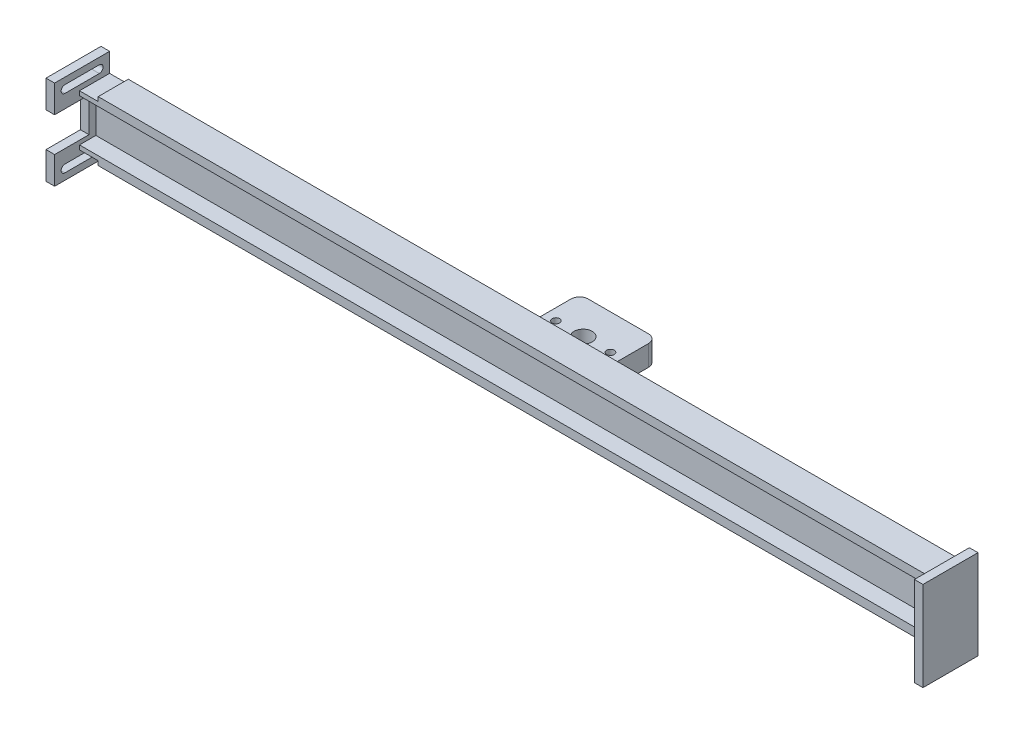
SolidWorks part; units mm, degrees
material "PLA"
ref_plane "Front Plane" through (0, 0, 0) normal (1, 0, 0) x (0, 1, 0)
ref_plane "Top Plane" through (0, 0, 0) normal (0, 0, 1) x (0, 1, 0)
ref_plane "Right Plane" through (0, 0, 0) normal (0, 1, 0) x (-1, 0, 0)
sketch "Sketch1" plane through (0, 0, 0) normal (1, 0, 0) x (0, 1, 0)
  line L16 (0, 4.7625) -> (-2.5, 4.7625)
  line L17 (0, 0) -> (12.3825, 0)
  line L18 (0, 0) -> (0, 4.7625)
  line L19 (0, 4.7625) -> (12.3825, 4.7625) construction
  line L20 (12.3825, 0) -> (12.3825, 4.7625)
  line L21 (-2.5, 4.7625) -> (-2.5, -4)
  line L22 (-2.5, -4) -> (14.8825, -4)
  line L23 (14.8825, -4) -> (14.8825, 4.7625)
  line L24 (12.3825, 4.7625) -> (14.8825, 4.7625)
  dimension "D1" = 4.7625
  dimension "D2" = 12.3825
  dimension "D3" = 2.5
extrude "Boss-Extrude1" add sketch "Sketch1" along normal blind 250
sketch "Sketch3" plane through (0, -2.5, 0) normal (0, -1, 0) x (1, 0, 0)
  line L0 (120.0194, -4) -> (129.9806, -4)
  line L1 (250, -4) -> (0, -4) construction
  line L2 (129.9806, -4) -> (129.9806, -9)
  line L3 (120.0194, -4) -> (120.0194, -10.1759)
  line L4 (0, 4.7625) -> (0, -4) construction
  arc A0 (120.0194, -10.1759) -> (129.9806, -9) centre (125.0694, -10.1759) ccw
  circle A1 centre (125.0694, -10.1759) radius 2.55
  point P5 (125, -4)
  dimension "D2" = 5.1
  dimension "D3" = 5
  dimension "D4" = 125
extrude "Boss-Extrude2" [suppressed] add sketch "Sketch3" against normal up to surface (17.3825 mm away) up to face at (125, 14.8825, 0.3813)
sketch "Sketch6" plane through (0, -2.5, 0) normal (0, -1, 0) x (1, 0, 0)
  line L0 (250, -4) -> (0, -4) construction
  line L1 (117.5385, -4) -> (131.3691, -4)
  line L2 (117.5385, -4) -> (117.5385, -13.6365)
  line L3 (117.5385, -13.6365) -> (131.3691, -13.6365)
  line L4 (131.3691, -4) -> (131.3691, -13.6365)
extrude "Cut-Extrude2" [suppressed] cut sketch "Sketch6" against normal blind 5
sketch "Sketch7" plane through (0, 14.8825, 0) normal (0, 1, 0) x (-1, 0, 0)
  line L0 (-250, -4) -> (0, -4) construction
  line L1 (-136.5723, -4) -> (-116.3235, -4)
  line L2 (-136.5723, -4) -> (-136.5723, -14.7915)
  line L3 (-136.5723, -14.7915) -> (-116.3235, -14.7915)
  line L4 (-116.3235, -4) -> (-116.3235, -14.7915)
extrude "Cut-Extrude3" [suppressed] cut sketch "Sketch7" against normal blind 5
sketch "Sketch8" [suppressed] plane through (250, 0, 0) normal (1, 0, 0) x (0, 1, 0)
  line L0 (6.1913, 0) -> (6.1913, -4) construction
  line L5 (12.3825, 0) -> (0, 0) construction
  line L6 (14.8825, -4) -> (-2.5, -4) construction
  line L11 (0, -3) -> (12.3825, -3)
  line L12 (0, -3) -> (0, -1)
  line L13 (0, -1) -> (12.3825, -1)
  line L14 (12.3825, -3) -> (12.3825, -1)
  line L15 (0, -3) -> (12.3825, -1) construction
  line L16 (0, -1) -> (12.3825, -3) construction
  point P6 (6.1913, -2)
  dimension "D1" = 12.3825
extrude "Cut-Extrude4" [suppressed] cut sketch "Sketch8" against normal through all
sketch "Sketch9" [suppressed] plane through (0, 0, -4) normal (0, 0, -1) x (-1, 0, 0)
  line L0 (-117.5194, -2.5) -> (-117.5194, 14.8825) construction
  line L1 (-120.0194, -2.5) -> (0, -2.5) construction
  line L2 (-120.0194, 14.8825) -> (0, 14.8825) construction
  line L3 (-120.0194, 14.8825) -> (-120.0194, -2.5) construction
  line L4 (-116.5194, 12.3825) -> (-118.5194, 12.3825)
  line L5 (-116.5194, 12.3825) -> (-116.5194, 0)
  line L6 (-116.5194, 0) -> (-118.5194, 0)
  line L7 (-118.5194, 12.3825) -> (-118.5194, 0)
  line L8 (-116.5194, 12.3825) -> (-118.5194, 0) construction
  line L9 (-116.5194, 0) -> (-118.5194, 12.3825) construction
  point P6 (-117.5194, 6.1913)
  dimension "D3" = 2.5
  dimension "D1" = 12.3825
extrude "Cut-Extrude5" [suppressed] cut sketch "Sketch9" against normal up to next
ref_plane "Plane1" through (125.0694, 0, 0) normal (-1, 0, 0) x (0, 0, 1)
mirror "Mirror1" [suppressed] about plane through (125.0694, 0, 0) normal (-1, 0, 0)
sketch "Sketch10" plane through (0, 0, 4.7625) normal (0, 0, 1) x (1, 0, 0)
  line L1 (0, 14.8825) -> (2.5, 14.8825)
  line L2 (0, 14.8825) -> (0, 18.8912)
  line L3 (0, 18.8912) -> (2.5, 18.8912)
  line L4 (2.5, 14.8825) -> (2.5, 18.8912)
  line L5 (0, -2.5) -> (2.5, -2.5)
  line L6 (0, -2.5) -> (0, -6.5088)
  line L7 (0, -6.5088) -> (2.5, -6.5088)
  line L8 (2.5, -2.5) -> (2.5, -6.5088)
  dimension "D2" = 25.4
extrude "Boss-Extrude3" [suppressed] add sketch "Sketch10" against normal up to surface (8.7625 mm away) up to face at (125, 6.1913, -4)
mirror "Mirror2" [suppressed] about plane through (125.0694, 0, 0) normal (-1, 0, 0)
sketch "Sketch11" [suppressed] plane through (250.1388, 0, 0) normal (1, 0, 0) x (0, 1, 0)
  circle A0 centre (16.3513, -1.46) radius 1.25 construction
  circle A1 centre (-3.9687, -1.46) radius 1.25 construction
  circle A2 centre (16.3513, -1.46) radius 1.25
  circle A3 centre (-3.9687, -1.46) radius 1.25
extrude "Cut-Extrude6" [suppressed] cut sketch "Sketch11" against normal up to surface (2.5 mm away)
mirror "Mirror3" [suppressed] about plane through (125.0694, 0, 0) normal (-1, 0, 0)
sketch "Sketch14" [suppressed] plane through (0, 0, 4.7625) normal (0, 0, 1) x (1, 0, 0)
  line L0 (0, 6.1912) -> (17.1619, 6.1912) construction
  line L1 (0, -6.5088) -> (3, -6.5088)
  line L2 (0, -6.5088) -> (0, -1.5088)
  line L3 (0, -1.5088) -> (3, -1.5088)
  line L4 (3, -6.5088) -> (3, -1.5088)
  line L5 (0, 12.3825) -> (0, 0) construction
  line L6 (0, 13.8912) -> (3, 13.8912)
  line L7 (3, 18.8912) -> (3, 13.8912)
  line L8 (0, 18.8912) -> (3, 18.8912)
  line L9 (0, 18.8912) -> (0, 13.8912)
  dimension "D2" = 3
extrude "Cut-Extrude7" [suppressed] cut sketch "Sketch14" against normal blind 4
mirror "Mirror4" [suppressed] about plane through (125.0694, 0, 0) normal (-1, 0, 0)
sketch "Sketch15" [suppressed] plane through (0, -2.5, 0) normal (0, -1, 0) x (-1, 0, 0)
  line L0 (-3, -0.7625) -> (-2.5, -0.7625) construction
  line L1 (-2.5, 4) -> (-6, 4)
  line L2 (-2.5, 4) -> (-2.5, -0.7625)
  line L3 (-2.5, -0.7625) -> (-6, -0.7625)
  line L4 (-6, 4) -> (-6, -0.7625)
  line L5 (0, 4) -> (0, -0.7625) construction
  dimension "D1" = 6
extrude "Cut-Extrude9" [suppressed] cut sketch "Sketch15" against normal blind 1 contours L4 L3 L2 L1
ref_plane "Plane3" through (0, 6.1913, 0) normal (0, 1, 0) x (1, 0, 0)
mirror "Mirror7" [suppressed] about plane through (0, 6.1913, 0) normal (0, 1, 0)
sketch "Sketch16" plane through (0, -2.5, 0) normal (0, -1, 0) x (1, 0, 0)
  line L0 (250, -4) -> (0, -4) construction
  line L1 (125, -4) -> (125, -29.4) construction
  line L2 (113.75, -4) -> (136.25, -4)
  line L3 (113.75, -4) -> (113.75, -29.4)
  line L4 (113.75, -29.4) -> (136.25, -29.4)
  line L5 (136.25, -4) -> (136.25, -29.4)
  line L6 (250, -4) -> (0, -4) construction
  line L7 (117.0625, -16.7) -> (132.9375, -16.7) construction
  circle A0 centre (117.0625, -16.7) radius 1.1
  circle A1 centre (132.9375, -16.7) radius 1.1
  circle A2 centre (125, -16.7) radius 2.65
  point P8 (125, -4)
  point P13 (125, -16.7)
  dimension "D4" = 2.2
  dimension "D5" = 2.2
  dimension "D6" = 5.3
  dimension "D2" = 15.875
  dimension "D3" = 22.5
  dimension "D1" = 12.7
extrude "Boss-Extrude4" add sketch "Sketch16" against normal blind 6
sketch "Sketch17" plane through (0, 0, -29.4) normal (0, 0, -1) x (1, 0, 0)
  line L4 (136.25, 2.5) -> (113.75, 2.5)
  line L5 (113.75, 2.5) -> (113.75, -3.5)
  line L6 (113.75, -3.5) -> (136.25, -3.5)
  line L7 (136.25, -3.5) -> (136.25, 2.5)
  line L8 (136.25, 2.5) -> (113.75, 2.5)
  line L9 (113.75, 2.5) -> (113.75, -3.5)
  line L10 (113.75, -3.5) -> (136.25, -3.5)
  line L11 (136.25, -3.5) -> (136.25, 2.5)
  dimension "D1" = 0
extrude "Cut-Extrude10" cut sketch "Sketch17" against normal blind 2.5
sketch "Sketch20" plane through (0, 0, 0) normal (-1, 0, 0) x (0, -1, 0)
  line L0 (2.5, -4) -> (-14.8825, -4) construction
  line L1 (-19.1913, -4) -> (6.8087, -4)
  line L2 (-19.1913, -4) -> (-19.1913, 12)
  line L3 (-19.1913, 12) -> (6.8087, 12)
  line L4 (6.8087, -4) -> (6.8087, 12)
  line L5 (-6.1913, 12) -> (-6.1913, -4) construction
  line L7 (-6.1913, 0) -> (-6.1913, -4) construction
  line L8 (-12.3825, 0) -> (0, 0) construction
  dimension "D1" = 26
  dimension "D2" = 16
extrude "Boss-Extrude7" add sketch "Sketch20" along normal blind 2.5
sketch "Sketch21" plane through (-2.5, 0, 0) normal (-1, 0, 0) x (0, -1, 0)
  line L0 (-6.1913, 12) -> (-6.1913, -4) construction
  line L1 (6.8087, 12) -> (-19.1913, 12) construction
  line L2 (-19.1913, -4) -> (6.8087, -4) construction
  line L3 (-16.1913, 9) -> (3.8087, 9) construction
  line L4 (-16.1913, 9) -> (-16.1913, -1) construction
  line L5 (-15.0913, 9) -> (-15.0913, -1)
  line L6 (-17.2913, 9) -> (-17.2913, -1)
  line L7 (3.8087, 9) -> (3.8088, -1) construction
  line L8 (2.7088, 9) -> (2.7088, -1)
  line L9 (4.9087, 9) -> (4.9087, -1)
  arc A2 (-15.0913, 9) -> (-17.2913, 9) centre (-16.1913, 9) ccw
  arc A3 (-17.2913, -1) -> (-15.0913, -1) centre (-16.1913, -1) ccw
  arc A4 (2.7088, 9) -> (4.9087, 9) centre (3.8087, 9) cw
  arc A5 (4.9087, -1) -> (2.7088, -1) centre (3.8088, -1) cw
  point P9 (-6.1913, 9)
  point P10 (-16.1913, 4)
  point P16 (3.8087, 4)
  dimension "D1" = 1.1
  dimension "D2" = 20
  dimension "D4" = 10
  dimension "D3" = 13
extrude "Cut-Extrude12" cut sketch "Sketch21" against normal blind 2.5
sketch "Sketch22" plane through (-2.5, 0, 0) normal (-1, 0, 0) x (0, -1, 0)
  line L0 (-6.1913, 12) -> (-6.1913, -4) construction
  line L1 (6.8087, 12) -> (-19.1913, 12) construction
  line L2 (-19.1913, -4) -> (6.8087, -4) construction
  line L4 (-11.1913, 2) -> (-1.1913, 2)
  line L5 (-11.1913, 2) -> (-11.1913, 12)
  line L6 (-11.1913, 12) -> (-1.1913, 12)
  line L7 (-1.1913, 2) -> (-1.1913, 12)
  line L8 (-11.1913, 2) -> (-1.1913, 12) construction
  line L9 (-11.1913, 12) -> (-1.1913, 2) construction
  point P6 (-6.1913, 7)
  dimension "D1" = 10
  dimension "D2" = 10
extrude "Cut-Extrude13" cut sketch "Sketch22" against normal blind 10
sketch "Sketch23" plane through (0, 14.8825, 0) normal (0, 1, 0) x (-1, 0, 0)
  line L0 (-250, -4) -> (0, -4) construction
  line L1 (0, 4.7625) -> (-5.4373, 4.7625)
  line L2 (0, 4.7625) -> (0, -4)
  line L3 (0, -4) -> (-5.4373, -4)
  line L4 (-5.4373, 4.7625) -> (-5.4373, -4)
extrude "Cut-Extrude14" cut sketch "Sketch23" against normal blind 1.25
mirror "Mirror8" about plane through (0, 6.1913, 0) normal (0, 1, 0) of "Cut-Extrude14"
sketch "Sketch24" plane through (250, 0, 0) normal (1, 0, 0) x (0, 1, 0)
  line L1 (-6.8087, -4) -> (19.1913, -4)
  line L2 (-6.8087, -4) -> (-6.8087, 12)
  line L3 (-6.8087, 12) -> (19.1913, 12)
  line L4 (19.1913, -4) -> (19.1913, 12)
extrude "Boss-Extrude8" add sketch "Sketch24" along normal blind 2.5
fillet "Fillet1" radius 2.5 2 edges at (136.25, 0.5, -26.9) (113.75, 0.5, -26.9)
equation "\"D1@Sketch1\"=\"ball_diameter\" * 0.25"
equation "\"D2@Sketch1\"=\"ball_diameter\" * 0.65"
equation "\"D3@Sketch1\"=\"wall_thickness\""
equation "\"D4@Sketch1\"=0.4cm"
equation "\"D1@Boss-Extrude1\"=\"track_length\""
equation "\"D2@Sketch3\"=\"axle\" + 0.01"
equation "\"ball_diameter\"= 0.75in"
equation "\"wall_thickness\" = 0.25cm"
equation "\"track_length\" = 25cm"
equation "\"axle\" = 5mm"
equation "\"D3@Sketch3\"=\"axle\" * 1"
equation "\"D4@Sketch3\"=\"track_length\" / 2"
equation "\"pillar_width\" = 2.75cm"
equation "\"D1@Sketch9\"=\"ball_diameter\" * 0.65"
equation "\"D1@Sketch8\"=\"ball_diameter\"*0.65"
equation "\"D1@Sketch10\"=\"wall_thickness\""
equation "\"D2@Sketch14\"=0.3"
equation "\"D5@Sketch16\"=\"D4@Sketch16\""
